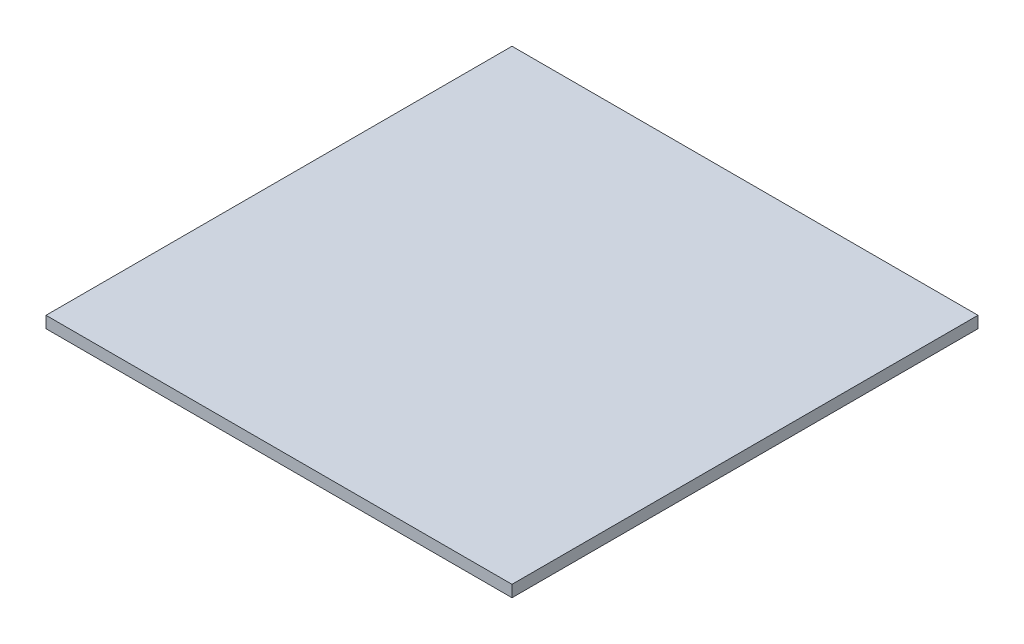
SolidWorks part; units mm, degrees
ref_plane "Front Plane" through (0, 0, 0) normal (0, 0, 1) x (1, 0, 0)
ref_plane "Top Plane" through (0, 0, 0) normal (0, 1, 0) x (1, 0, 0)
ref_plane "Right Plane" through (0, 0, 0) normal (1, 0, 0) x (0, 0, -1)
sketch "Sketch1" plane through (0, 0, 0) normal (0, 1, 0) x (1, 0, 0)
  line L1 (-100, 100) -> (100, 100)
  line L2 (-100, 100) -> (-100, -100)
  line L3 (-100, -100) -> (100, -100)
  line L4 (100, 100) -> (100, -100)
  line L5 (-100, 100) -> (100, -100) construction
  line L6 (-100, -100) -> (100, 100) construction
  point P0 (0, 0)
  dimension "D1" = 200
  dimension "D2" = 200
extrude "Base" add sketch "Sketch1" along normal blind 2.5 and the other way blind 2.5
sketch "Sketch2" plane through (0, -2.5, 0) normal (0, -1, 0) x (-1, 0, 0)
  line L0 (45, -47.5) -> (-45, -47.5)
  line L1 (42.5, -37.5) -> (-42.5, -37.5)
  line L2 (42.5, -37.5) -> (42.5, 37.5)
  line L3 (42.5, 37.5) -> (-42.5, 37.5)
  line L4 (-42.5, -37.5) -> (-42.5, 37.5)
  line L5 (-113.4478, 0) -> (141.2128, 0) construction
  line L6 (0, -175.8738) -> (0, 153.5398) construction
  line L7 (-45, -47.5) -> (-45, 47.5)
  line L8 (45, 47.5) -> (-45, 47.5)
  line L9 (45, -47.5) -> (45, 47.5)
  dimension "D1" = 75
  dimension "D2" = 85
  dimension "D3" = 2.5
  dimension "D4" = 2.5
  dimension "D5" = 10
  dimension "D6" = 10
extrude "BatteryHolder" add sketch "Sketch2" along normal blind 25
